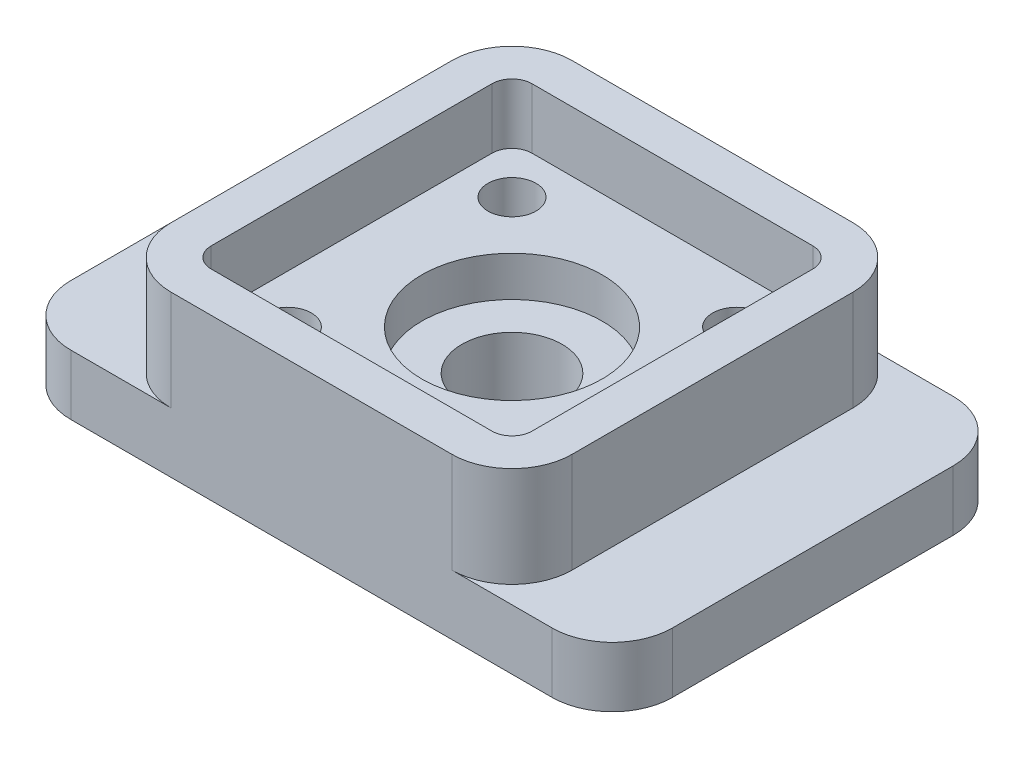
SolidWorks part; units mm, degrees
ref_plane "Alzado" through (0, 0, 0) normal (0, 0, 1) x (1, 0, 0)
ref_plane "Planta" through (0, 0, 0) normal (0, 1, 0) x (1, 0, 0)
ref_plane "Vista lateral" through (0, 0, 0) normal (1, 0, 0) x (0, 0, -1)
sketch "Croquis1" plane through (0, 0, 0) normal (0, 1, 0) x (1, 0, 0)
  line L0 (0, 0) -> (0, -114.7989) construction
  line L1 (0, 0) -> (111.7816, 0) construction
  line L2 (0, 0) -> (0, 124.3103) construction
  line L3 (-60, -50) -> (60, -50) construction
  line L4 (75, -35) -> (75, 35) construction
  line L5 (60, 50) -> (-60, 50) construction
  line L6 (-75, 35) -> (-75, -35) construction
  line L7 (0, 0) -> (0, -89.1953) construction
  line L8 (0, 0) -> (-209.0702, 0) construction
  line L9 (0, 0) -> (0, 149.9139) construction
  line L10 (-35, -40) -> (35, -40) construction
  line L11 (40, -35) -> (40, 35) construction
  line L12 (35, 40) -> (-35, 40) construction
  line L13 (-40, 35) -> (-40, -35) construction
  line L14 (0, 0) -> (0, -80.8333) construction
  line L15 (0, 0) -> (-274.4532, 0) construction
  line L16 (0, 0) -> (0, 158.2759) construction
  line L17 (-35, -50) -> (35, -50) construction
  line L18 (50, -35) -> (50, 35) construction
  line L19 (35, 50) -> (-35, 50) construction
  line L20 (-50, 35) -> (-50, -35) construction
  arc A0 (60, -50) -> (75, -35) centre (60, -35) ccw construction
  arc A1 (75, 35) -> (60, 50) centre (60, 35) ccw construction
  arc A2 (-60, 50) -> (-75, 35) centre (-60, 35) ccw construction
  arc A3 (-75, -35) -> (-60, -50) centre (-60, -35) ccw construction
  circle A4 centre (-60, 35) radius 7.5 construction
  circle A5 centre (60, 35) radius 7.5 construction
  circle A6 centre (-60, -35) radius 7.5 construction
  circle A7 centre (60, -35) radius 7.5 construction
  circle A8 centre (60, 35) radius 5 construction
  circle A9 centre (60, -35) radius 5 construction
  circle A10 centre (-60, -35) radius 5 construction
  circle A11 centre (-60, 35) radius 5 construction
  arc A12 (35, -40) -> (40, -35) centre (35, -35) ccw construction
  arc A13 (40, 35) -> (35, 40) centre (35, 35) ccw construction
  arc A14 (-35, 40) -> (-40, 35) centre (-35, 35) ccw construction
  arc A15 (-40, -35) -> (-35, -40) centre (-35, -35) ccw construction
  circle A20 centre (-28, 28) radius 6 construction
  circle A21 centre (28, 28) radius 6 construction
  circle A22 centre (28, -28) radius 6 construction
  circle A23 centre (-28, -28) radius 6 construction
  circle A24 centre (0, 0) radius 12.5 construction
  circle A25 centre (0, 0) radius 22.5 construction
  arc A26 (35, -50) -> (50, -35) centre (35, -35) ccw construction
  arc A27 (50, 35) -> (35, 50) centre (35, 35) ccw construction
  arc A28 (-35, 50) -> (-50, 35) centre (-35, 35) ccw construction
  arc A29 (-50, -35) -> (-35, -50) centre (-35, -35) ccw construction
  point P8 (0, -50)
  point P22 (75, 0)
  point P34 (0, -40)
  point P48 (40, 0)
  point P62 (0, -50)
  point P71 (50, 0)
  point P73 (0, 0)
  dimension "D1" = 15
  dimension "D4" = 15
  dimension "D5" = 10
  dimension "D6" = 5
  dimension "D9" = 12
  dimension "D18" = 25
  dimension "D19" = 45
  dimension "D20" = 15
  dimension "D2" = 150
  dimension "D3" = 100
  dimension "D7" = 80
  dimension "D8" = 80
  dimension "D10" = 56
  dimension "D11" = 56
  dimension "D12" = 56
  dimension "D13" = 56
  dimension "D14" = 28
  dimension "D15" = 28
  dimension "D16" = 28
  dimension "D17" = 28
  dimension "D21" = 100
  dimension "D22" = 100
sketch "Croquis3" plane through (0, 0, 0) normal (0, 1, 0) x (1, 0, 0)
  line L0 (60, 50) -> (-60, 50) construction
  line L1 (75, -35) -> (75, 35) construction
  line L2 (-60, -50) -> (60, -50) construction
  line L3 (-75, 35) -> (-75, -35) construction
  line L4 (60, 50) -> (-60, 50)
  line L5 (75, -35) -> (75, 35)
  line L6 (-60, -50) -> (60, -50)
  line L7 (-75, 35) -> (-75, -35)
  circle A0 centre (0, 0) radius 12.5 construction
  circle A1 centre (-28, -28) radius 6 construction
  circle A2 centre (-28, 28) radius 6 construction
  circle A3 centre (28, 28) radius 6 construction
  circle A4 centre (60, 35) radius 5 construction
  circle A5 centre (60, -35) radius 5 construction
  circle A6 centre (-60, -35) radius 5 construction
  circle A7 centre (-60, 35) radius 5 construction
  arc A8 (-60, 50) -> (-75, 35) centre (-60, 35) ccw construction
  arc A9 (75, 35) -> (60, 50) centre (60, 35) ccw construction
  arc A10 (60, -50) -> (75, -35) centre (60, -35) ccw construction
  arc A11 (-75, -35) -> (-60, -50) centre (-60, -35) ccw construction
  circle A12 centre (0, 0) radius 12.5
  circle A13 centre (-28, -28) radius 6
  circle A14 centre (-28, 28) radius 6
  circle A15 centre (28, 28) radius 6
  circle A16 centre (60, 35) radius 5
  circle A17 centre (60, -35) radius 5
  circle A18 centre (-60, -35) radius 5
  circle A19 centre (-60, 35) radius 5
  arc A20 (-60, 50) -> (-75, 35) centre (-60, 35) ccw
  arc A21 (75, 35) -> (60, 50) centre (60, 35) ccw
  arc A22 (60, -50) -> (75, -35) centre (60, -35) ccw
  arc A23 (-75, -35) -> (-60, -50) centre (-60, -35) ccw
extrude "Saliente-Extruir1" add sketch "Croquis3" along normal blind 15
sketch "Croquis4" plane through (0, 0, 0) normal (0, 1, 0) x (1, 0, 0)
  circle A0 centre (60, -35) radius 7.5 construction
  circle A1 centre (60, 35) radius 7.5 construction
  circle A2 centre (-60, 35) radius 7.5 construction
  circle A3 centre (-60, -35) radius 7.5 construction
  circle A4 centre (60, -35) radius 7.5
  circle A5 centre (60, 35) radius 7.5
  circle A6 centre (-60, 35) radius 7.5
  circle A7 centre (-60, -35) radius 7.5
extrude "Saliente-Extruir2" add sketch "Croquis4" against normal blind 2 from surface starting at face at (-60, 15, 40)
sketch "Croquis5" plane through (0, 0, 0) normal (0, 1, 0) x (1, 0, 0)
  line L0 (35, 40) -> (-35, 40) construction
  line L1 (50, -35) -> (50, 35) construction
  line L2 (-35, -40) -> (35, -40) construction
  line L3 (-50, 35) -> (-50, -35) construction
  line L4 (35, 40) -> (-35, 40)
  line L5 (50, -35) -> (50, 35)
  line L6 (-35, -40) -> (35, -40)
  line L7 (-50, 35) -> (-50, -35)
  line L8 (40, -35) -> (40, 35) construction
  line L9 (-40, 35) -> (-40, -35) construction
  line L10 (40, -35) -> (40, 35)
  line L11 (-40, 35) -> (-40, -35)
  line L12 (60, 50) -> (-60, 50) construction
  line L13 (-60, -50) -> (60, -50) construction
  line L14 (35, 50) -> (-35, 50)
  line L15 (-35, -50) -> (35, -50)
  arc A0 (50, 35) -> (35, 50) centre (35, 35) ccw construction
  arc A1 (-35, 50) -> (-50, 35) centre (-35, 35) ccw construction
  arc A2 (35, -50) -> (50, -35) centre (35, -35) ccw construction
  arc A3 (-50, -35) -> (-35, -50) centre (-35, -35) ccw construction
  arc A4 (50, 35) -> (35, 50) centre (35, 35) ccw
  arc A5 (-35, 50) -> (-50, 35) centre (-35, 35) ccw
  arc A6 (35, -50) -> (50, -35) centre (35, -35) ccw
  arc A7 (-50, -35) -> (-35, -50) centre (-35, -35) ccw
  arc A8 (-35, 40) -> (-40, 35) centre (-35, 35) ccw construction
  arc A9 (35, -40) -> (40, -35) centre (35, -35) ccw construction
  arc A10 (-40, -35) -> (-35, -40) centre (-35, -35) ccw construction
  arc A11 (40, 35) -> (35, 40) centre (35, 35) ccw construction
  arc A12 (40, 35) -> (35, 40) centre (35, 35) ccw
  arc A13 (35, -40) -> (40, -35) centre (35, -35) ccw
  arc A14 (-40, -35) -> (-35, -40) centre (-35, -35) ccw
  arc A15 (-35, 40) -> (-40, 35) centre (-35, 35) ccw
extrude "Saliente-Extruir3" add sketch "Croquis5" along normal blind 40
sketch "Croquis6" plane through (0, 0, 0) normal (0, 1, 0) x (1, 0, 0)
  line L0 (-40, 35) -> (-40, -35) construction
  line L1 (35, 40) -> (-35, 40) construction
  line L2 (40, -35) -> (40, 35) construction
  line L3 (-35, -40) -> (35, -40) construction
  line L4 (-35, -40) -> (35, -40)
  line L5 (40, -35) -> (40, 35)
  line L6 (35, 40) -> (-35, 40)
  line L7 (-40, 35) -> (-40, -35)
  arc A0 (-35, 40) -> (-40, 35) centre (-35, 35) ccw construction
  arc A1 (40, 35) -> (35, 40) centre (35, 35) ccw construction
  arc A2 (35, -40) -> (40, -35) centre (35, -35) ccw construction
  arc A3 (-40, -35) -> (-35, -40) centre (-35, -35) ccw construction
  circle A4 centre (0, 0) radius 22.5 construction
  circle A5 centre (28, 28) radius 6 construction
  circle A6 centre (28, -28) radius 6 construction
  circle A7 centre (-28, -28) radius 6 construction
  circle A8 centre (-28, 28) radius 6 construction
  circle A9 centre (0, 0) radius 22.5
  circle A10 centre (28, 28) radius 6
  circle A11 centre (28, -28) radius 6
  circle A12 centre (-28, -28) radius 6
  circle A13 centre (-28, 28) radius 6
  arc A14 (-40, -35) -> (-35, -40) centre (-35, -35) ccw
  arc A15 (35, -40) -> (40, -35) centre (35, -35) ccw
  arc A16 (40, 35) -> (35, 40) centre (35, 35) ccw
  arc A17 (-35, 40) -> (-40, 35) centre (-35, 35) ccw
extrude "Saliente-Extruir4" add sketch "Croquis6" along normal blind 25
